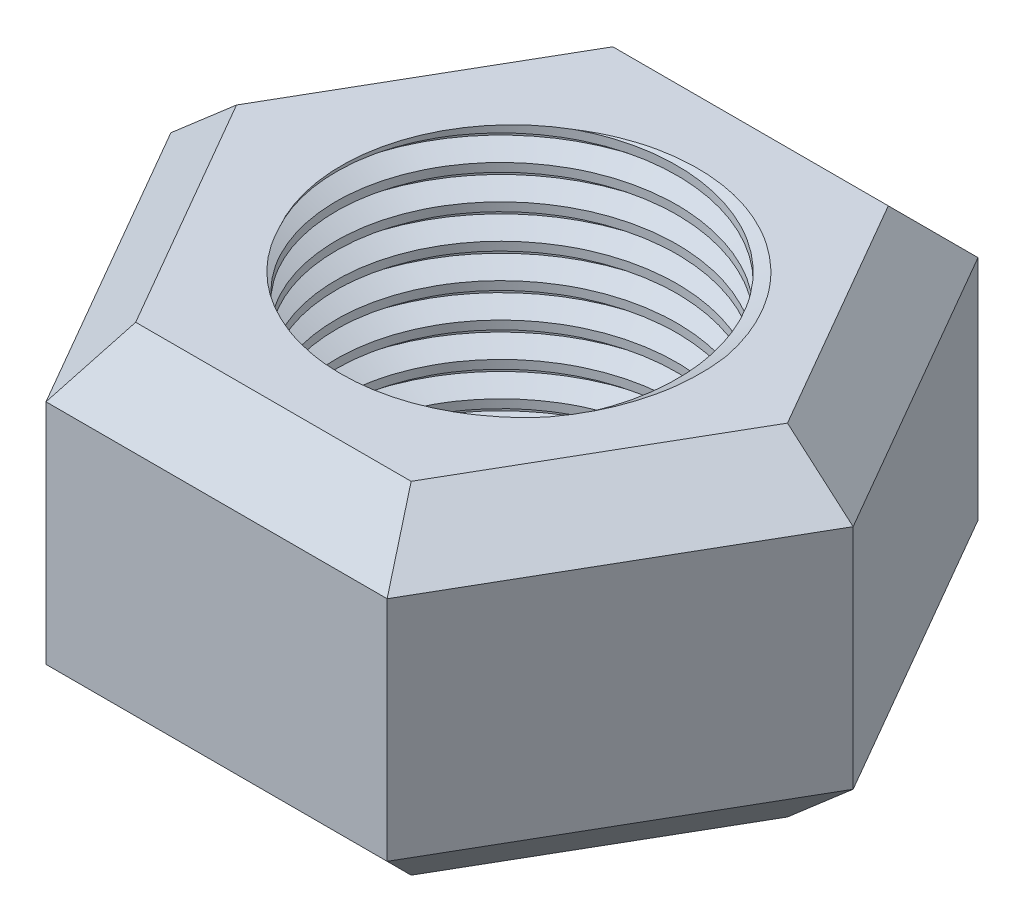
SolidWorks part; units mm, degrees
ref_plane "Front Plane" through (0, 0, 0) normal (0, 0, 1) x (1, 0, 0)
ref_plane "Top Plane" through (0, 0, 0) normal (0, 1, 0) x (1, 0, 0)
ref_plane "Right Plane" through (0, 0, 0) normal (1, 0, 0) x (0, 0, -1)
sketch "Sketch1" plane through (0, 0, 0) normal (0, 1, 0) x (1, 0, 0)
  line L1 (1.5, 2.5981) -> (-1.5, 2.5981)
  line L2 (-1.5, 2.5981) -> (-3, 0)
  line L3 (-3, 0) -> (-1.5, -2.5981)
  line L4 (-1.5, -2.5981) -> (1.5, -2.5981)
  line L5 (1.5, -2.5981) -> (3, 0)
  line L6 (3, 0) -> (1.5, 2.5981)
  circle A0 centre (0, 0) radius 2.5981 construction
  circle A1 centre (0, 0) radius 1.5
  dimension "D1" = 3
  dimension "D2" = 3
extrude "Boss-Extrude1" add sketch "Sketch1" along normal blind 3
chamfer "Chamfer1" distance 0.5 angle 45 12 edges at (2.25, 3, 1.299) (0, 3, 2.5981) (-2.25, 3, 1.299) (-2.25, 3, -1.299) (0, 3, -2.5981) (2.25, 3, -1.299) (0, 0, -2.5981) (-2.25, 0, -1.299) (-2.25, 0, 1.299) (0, 0, 2.5981) (2.25, 0, 1.299) (2.25, 0, -1.299)
thread "Thread1" pitch 0.3 start angle 0, offset 1, length 0, pitch 0.3, diameter 3
ref_plane "Plane1" through (1.5, -1, 0) normal (0, 0, 1) x (1, 0, 0)
sketch "Thread Profile1" plane through (1.5, -1, 0) normal (0, 0, 1) x (1, 0, 0)
  line L0 (0, 0) -> (0, 0.3) construction
  line L1 (0, 0) -> (0.1624, 0.0937)
  line L2 (0.1624, 0.0937) -> (0.1624, 0.1312)
  line L3 (0.1624, 0.1312) -> (0, 0.225)
  line L4 (0.1624, 0.1125) -> (0, 0.1125) construction
  line L11 (0, 0) -> (0, 0.225)
  point P2 (0, 0)
  dimension "Pitch" = 0.3
  dimension "Profile_Angle" = 60
  dimension "Profile_Land" = 0.0375
  dimension "Profile_Height" = 0.1624
